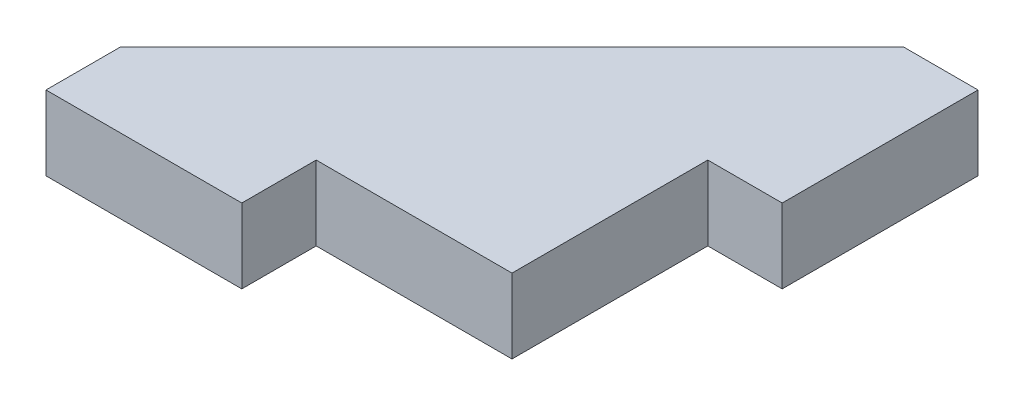
SolidWorks part; units mm, degrees
ref_plane "Front Plane" through (0, 0, 0) normal (0, 0, 1) x (1, 0, 0)
ref_plane "Top Plane" through (0, 0, 0) normal (0, 1, 0) x (1, 0, 0)
ref_plane "Right Plane" through (0, 0, 0) normal (1, 0, 0) x (0, 0, -1)
sketch "Sketch1" plane through (0, 0, 0) normal (0, 1, 0) x (1, 0, 0)
  line L0 (-21.062, -13.6221) -> (4.338, 11.7779)
  line L2 (4.338, 11.7779) -> (9.164, 11.7779)
  line L3 (-21.062, -13.6221) -> (4.338, -13.6221)
  line L4 (4.338, 11.7779) -> (4.338, -13.6221)
  line L5 (4.338, 11.7779) -> (4.338, -0.9221)
  line L6 (4.338, -0.9221) -> (9.164, -0.9221)
  line L7 (9.164, 11.7779) -> (9.164, -0.9221)
  line L8 (-21.062, -13.6221) -> (-8.362, -13.6221)
  line L9 (-21.062, -13.6221) -> (-21.062, -18.4481)
  line L10 (-21.062, -18.4481) -> (-8.362, -18.4481)
  line L11 (-8.362, -13.6221) -> (-8.362, -18.4481)
  dimension "D2" = 25.4
  dimension "D3" = 12.7
  dimension "D4" = 4.826
  dimension "D5" = 4.826
extrude "Boss-Extrude1" add sketch "Sketch1" along normal blind 4.826 contours L11 L3 L9 L10 | L4 L0 L3 | L7 L2 L4 L6 region at (-4.1287, 0, 5.1554) region at (-14.712, 0, 16.0351) region at (6.751, 0, -5.4279)
equation "\"MDF\"= 0.19in"
equation "\"Foamcore\"= .13in"
equation "\"Gmaterial\"= \"MDF\""
equation "\"D4@Sketch1\"=\"MDF\""
equation "\"D5@Sketch1\"=\"MDF\""
equation "\"D1@Boss-Extrude1\"=\"MDF\""
equation "\"PVCID\" = 2.067in"
equation "\"PVCOD\" = 2.375in"
equation "\"GenDiameter\"= 60mm"
equation "\"GenCutDiameter\" = 1.8in"
equation "\"GenCutDistance\" = 1"
equation "\"TowerHeight\" = 6in"
equation "\"TowerFrontBase\" = 3in"
equation "\"FunnelHeight\" = 1in"
equation "\"FunnelAngle\" = 20"
equation "\"TowerSideBase\" = 3in"
equation "\"TowerPanelLength\" = 2in"
equation "\"TowerPanelLeeway\" = 0.5in"
equation "\"BaseLength\" = 10in"
equation "\"BaseWidth\" = 10.5in"
equation "\"WheelHoleLength\" = 3.25in"
equation "\"WheelHoleWidth\" = 26mm"
equation "\"WheelHoleFromBack\" = 1in"
equation "\"DropLength\" = 1in"
equation "\"DropWidth\" = 8.5in"
equation "\"BumperWidth\" = 1in"
equation "\"HoleDiameter\"= 0.25in"
equation "\"SmallHexDiameter\" = 0.185in"
equation "\"SmallHexHeight\" = 0.701in"
equation "\"ScrewSize\" = 0.106in"
equation "\"BigHexDiameter\" = 0.251in"
equation "\"BigHexHeight\" = 0.374in"
equation "\"PCBThickness\" = 0.066in"
equation "\"ConnectorHeight\" = 0.517in"
equation "\"BoardHeight\" = 0.583in"
equation "\"UnoStackHeight\" = 1.351in"
equation "\"UnoStackWidth\" = 3.053in"
equation "\"UnoStackLength\" = 3.152in"
equation "\"HBridgeWidth\" = 1.797in"
equation "\"HBridgeLength\" = 2.236in"
equation "\"DSWidth\" = 1.820in"
equation "\"DSLength\" = 1.833in"
equation "\"StepperWidth\" = 1.799in"
equation "\"StepperLength\" = 2.248in"
equation "\"ULNWidth\" = 1.304in"
equation "\"ULNLength\" = 1.545in"
equation "\"VSwitchHeight\" = 0.392in"
equation "\"VSwitchWidth\" = 0.637in"
equation "\"VSwitchLength\" = 1.097in"
equation "\"SkateWheelDiameter\" = 80mm"
equation "\"SkateWheelThickness\" = 24mm"
equation "\"BaseDistance\" = 3in"
